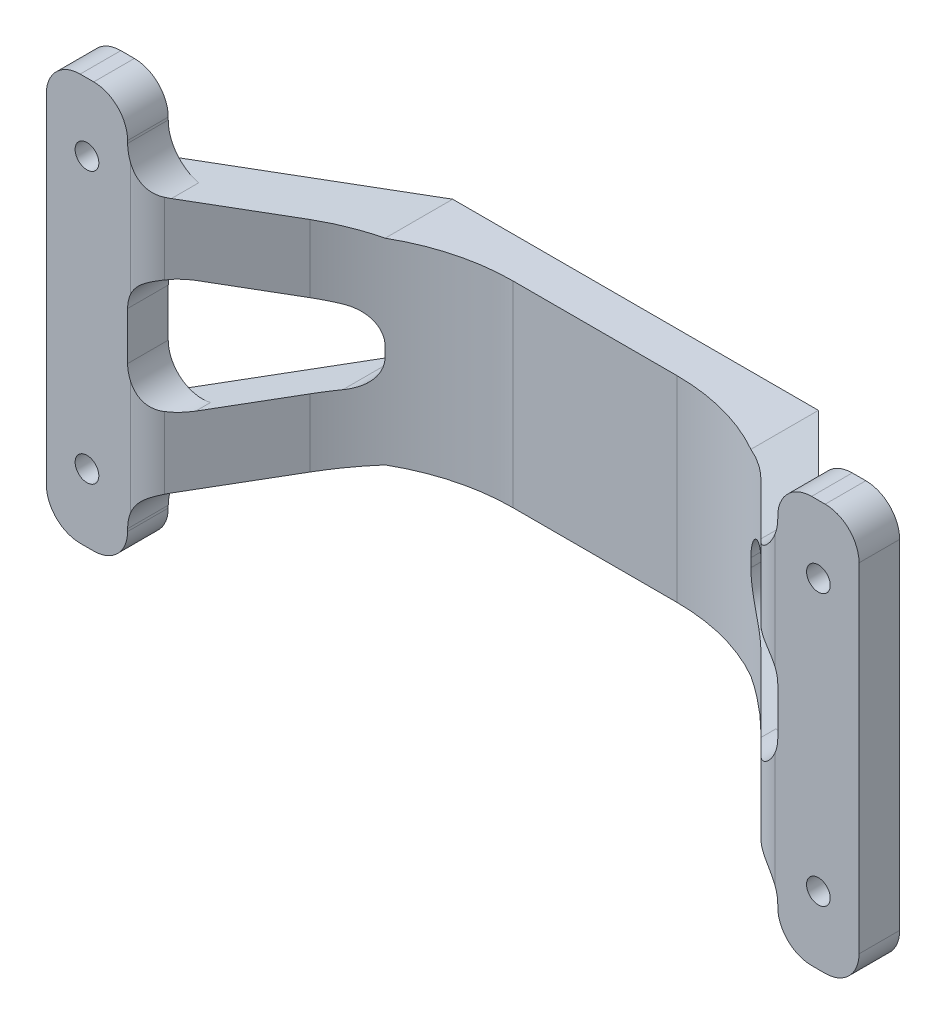
SolidWorks part; units mm, degrees
ref_plane "前视基准面" through (0, 0, 0) normal (0, 0, 1) x (1, 0, 0)
ref_plane "上视基准面" through (0, 0, 0) normal (0, 1, 0) x (1, 0, 0)
ref_plane "右视基准面" through (0, 0, 0) normal (1, 0, 0) x (0, 0, -1)
sketch "草图1" plane through (0, 0, 0) normal (0, 1, 0) x (1, 0, 0)
  line L14 (0, 315.0163) -> (0, -319.6154) construction
  line L15 (-24.5147, 0) -> (24.5147, 0)
  line L16 (24.5147, 0) -> (45.5147, -21)
  line L17 (45.5147, -21) -> (60, -21)
  line L18 (60, -21) -> (60, -15)
  line L19 (60, -15) -> (48, -15)
  line L20 (48, -15) -> (27, 6)
  line L21 (27, 6) -> (-27, 6)
  line L22 (-48, -15) -> (-27, 6)
  line L23 (-60, -15) -> (-48, -15)
  line L24 (-60, -21) -> (-60, -15)
  line L25 (-45.5147, -21) -> (-60, -21)
  line L26 (-24.5147, 0) -> (-45.5147, -21)
  point P2 (-63, 0)
  point P12 (0, 6)
  point P18 (0, 0)
  dimension "D1" = 120
  dimension "D2" = 135
  dimension "D3" = 6
  dimension "D4" = 15
  dimension "D5" = 6
  dimension "D6" = 12
  dimension "D7" = 6
extrude "凸台-拉伸1" add sketch "草图1" along normal blind 60
sketch "草图2" plane through (0, 0, -6) normal (0, 0, -1) x (-1, 0, 0)
  line L0 (0, 0) -> (0, 62.879) construction
  line L1 (-27, 0) -> (27, 0) construction
  line L2 (-60, 30) -> (68.4065, 30) construction
  line L3 (-60, 60) -> (-60, 0) construction
  line L4 (-48, 60) -> (-48, 50)
  line L5 (-48, 60) -> (-48, 0) construction
  line L6 (-48, 50) -> (-27, 44.5)
  line L7 (-27, 60) -> (-27, 0) construction
  line L8 (-27, 44.5) -> (27, 44.5)
  line L9 (-48, 60) -> (48, 60)
  line L10 (-27, 60) -> (27, 60) construction
  line L11 (48, 50) -> (27, 44.5)
  line L12 (48, 60) -> (48, 50)
  line L13 (48, 0) -> (48, 10)
  line L14 (48, 10) -> (27, 15.5)
  line L15 (-48, 0) -> (48, 0)
  line L16 (-27, 15.5) -> (27, 15.5)
  line L17 (-48, 10) -> (-27, 15.5)
  line L18 (-48, 0) -> (-48, 10)
  line L19 (48, 60) -> (48, 0) construction
  line L20 (-48, 40) -> (-27, 34.5)
  line L21 (-27, 34.5) -> (-27, 25.5)
  line L23 (-48, 20) -> (-48, 40)
  line L24 (-48, 20) -> (-27, 25.5)
  line L25 (48, 20) -> (27, 25.5)
  line L26 (27, 34.5) -> (27, 25.5)
  line L27 (48, 40) -> (27, 34.5)
  line L28 (48, 20) -> (48, 40)
  circle A0 centre (-54, 50) radius 1.75
  circle A1 centre (-54, 10) radius 1.75
  circle A2 centre (54, 10) radius 1.75
  circle A3 centre (54, 50) radius 1.75
  point P29 (0, 60)
  point P30 (0, 44.5)
  point P37 (0, 15.5)
  point P38 (0, 0)
  point P46 (-48, 30)
  point P47 (-27, 30)
  dimension "D1" = 40
  dimension "D2" = 108
  dimension "D3" = 3.5
  dimension "D4" = 29
  dimension "D5" = 10
  dimension "D6" = 10
extrude "切除-拉伸1" cut sketch "草图2" against normal blind 40
sketch "草图3" plane through (0, 0, 15) normal (0, 0, -1) x (-1, 0, 0)
  line L0 (-60, 30) -> (60, 30) construction
  line L1 (-60, 60) -> (-60, 0) construction
  line L2 (60, 60) -> (60, 0) construction
  line L3 (0, 44.5) -> (0, -2.6457) construction
  line L4 (-27, 44.5) -> (27, 44.5) construction
  circle A0 centre (-54, 50) radius 4
  circle A1 centre (-54, 10) radius 4
  circle A2 centre (54, 10) radius 4
  circle A3 centre (54, 50) radius 4
  dimension "D1" = 8
extrude "切除-拉伸2" cut sketch "草图3" against normal blind 2
sketch "草图4" plane through (0, 0, -6) normal (0, 0, -1) x (-1, 0, 0)
  line L0 (0, 44.5) -> (0, 15.5) construction
  line L1 (-27, 44.5) -> (27, 44.5) construction
  line L2 (27, 15.5) -> (-27, 15.5) construction
  circle A0 centre (0, 30) radius 2.5
  dimension "D1" = 5
extrude "切除-拉伸3" cut sketch "草图4" against normal blind 3
sketch "草图5" plane through (0, 0, -6) normal (0, 0, -1) x (-1, 0, 0)
  circle A0 centre (0, 30) radius 5
  circle A1 centre (0, 30) radius 2.5
  dimension "D1" = 10
extrude "凸台-拉伸2" add sketch "草图5" along normal blind 1
fillet "圆角1" radius 5 8 edges at (-48, 60, 18) (-60, 60, 18) (-48, 0, 18) (-60, 0, 18) (60, 0, 18) (48, 0, 18) (60, 60, 18) (48, 60, 18)
fillet "圆角2" radius 30 2 edges at (-24.5147, 30, 0) (24.5147, 30, 0)
fillet "圆角4" radius 2 4 edges at (-48, 45, 15) (-48, 15, 15) (48, 15, 15) (48, 45, 15)
fillet "圆角5" radius 5 4 edges at (-45.5147, 15.6509, 21) (-45.5147, 44.3491, 21) (45.5147, 44.3491, 21) (45.5147, 15.6509, 21)
fillet "圆角6" radius 6 4 edges at (48, 50, 18) (-48, 50, 18) (-48, 10, 18) (48, 10, 18)
fillet "圆角7" radius 5 8 edges at (-48, 20, 18) (-48, 40, 18) (48, 40, 18) (48, 20, 18) (27, 25.5, -1.0158) (27, 34.5, -1.0158) (-27, 25.5, -1.0158) (-27, 34.5, -1.0158)
